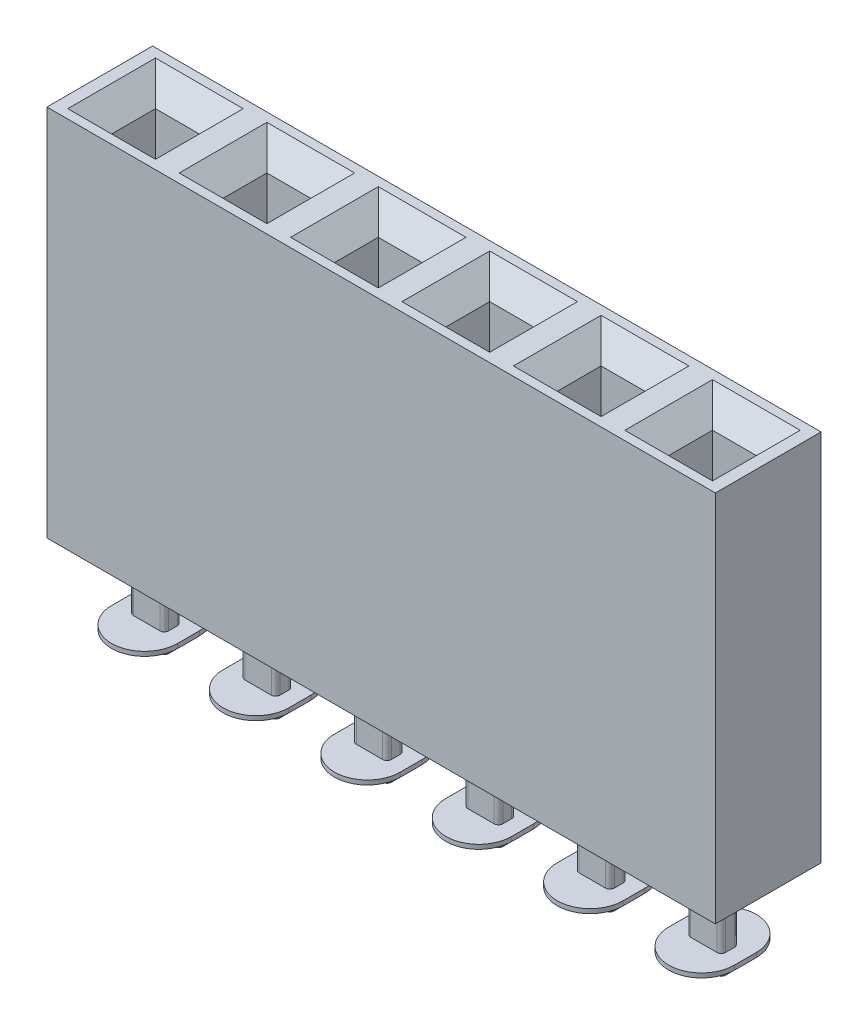
SolidWorks part; units mm, degrees
material "PA Type 6"
ref_plane "Front Plane" through (0, 0, 0) normal (0, 0, 1) x (1, 0, 0)
ref_plane "Top Plane" through (0, 0, 0) normal (0, 1, 0) x (1, 0, 0)
ref_plane "Right Plane" through (0, 0, 0) normal (1, 0, 0) x (0, 0, -1)
ref_plane "Plane1" through (0, -1.65, 0) normal (0, 1, 0) x (1, 0, 0)
sketch "Sketch2" plane through (0, 0, 0) normal (0, 1, 0) x (1, 0, 0)
  line L0 (0, -55) -> (0, 55) construction
  line L1 (-1.27, 1.205) -> (13.97, 1.205)
  line L2 (-1.27, 1.205) -> (-1.27, -1.205)
  line L3 (-1.27, -1.205) -> (13.97, -1.205)
  line L4 (13.97, 1.205) -> (13.97, -1.205)
  line L5 (-55, 0) -> (55, 0) construction
  dimension "D1" = 15.24
  dimension "D2" = 1.27
  dimension "D3" = 2.41
  dimension "D4" = 1.205
extrude "Boss-Extrude1" add sketch "Sketch2" along normal blind 8.51
sketch "Sketch5" plane through (0, 8.51, 0) normal (0, 1, 0) x (1, 0, 0)
  line L0 (-55, 0) -> (55, 0) construction
  line L1 (0.5, 0.5) -> (-0.5, 0.5)
  line L2 (0.5, 0.5) -> (0.5, -0.5)
  line L3 (0.5, -0.5) -> (-0.5, -0.5)
  line L4 (-0.5, 0.5) -> (-0.5, -0.5)
  line L5 (0, -55) -> (0, 55) construction
  dimension "D1" = 0.5
  dimension "D2" = 1
  dimension "D3" = 0.5
extrude "Cut-Extrude1" cut sketch "Sketch5" against normal blind 5
chamfer "Chamfer1" distance 0.5 angle 45 4 edges at (-0.5, 8.51, 0) (0, 8.51, 0.5) (0.5, 8.51, 0) (0, 8.51, -0.5)
pattern_linear "LPattern3" count 6 spacing 2.54 along (1, 0, 0) of "Chamfer1", "Cut-Extrude1"
sketch "Sketch8" plane through (0, 0, 0) normal (0, 1, 0) x (1, 0, 0)
  line L0 (0, -1.3255) -> (0, 1.3255) construction
  line L1 (-0.3, -0.2) -> (0.3, -0.2)
  line L2 (-0.4, -0.1) -> (-0.4, 0.1)
  line L3 (-0.3, 0.2) -> (0.3, 0.2)
  line L4 (0.4, -0.1) -> (0.4, 0.1)
  line L5 (-4.6805, 0) -> (4.6805, 0) construction
  arc A0 (-0.3, -0.2) -> (-0.4, -0.1) centre (-0.3, -0.1) cw
  arc A1 (0.3, -0.2) -> (0.4, -0.1) centre (0.3, -0.1) ccw
  arc A2 (0.3, 0.2) -> (0.4, 0.1) centre (0.3, 0.1) cw
  arc A3 (-0.4, 0.1) -> (-0.3, 0.2) centre (-0.3, 0.1) cw
  point P10 (-0.4, -0.2)
  point P13 (0.4, -0.2)
  point P16 (0.4, 0.2)
  dimension "D5" = 0.1
  dimension "D1" = 0.4
  dimension "D2" = 0.8
  dimension "D3" = 0.4
  dimension "D4" = 0.2
extrude "Boss-Extrude2" add sketch "Sketch8" against normal blind 2 separate body
sketch "Sketch10" plane through (0, -1.65, 0) normal (0, 1, 0) x (1, 0, 0)
  line L0 (0, -0.25) -> (0, 0.25) construction
  line L1 (0, -1.3255) -> (0, 1.3255) construction
  line L2 (-0.75, -0.25) -> (-0.75, 0.25)
  line L3 (0.75, -0.25) -> (0.75, 0.25)
  line L4 (-5.7805, 0) -> (5.7805, 0) construction
  arc A0 (-0.75, -0.25) -> (0.75, -0.25) centre (0, -0.25) ccw
  arc A1 (0.75, 0.25) -> (-0.75, 0.25) centre (0, 0.25) ccw
  point P5 (0, 0)
  dimension "D1" = 1.5
  dimension "D2" = 0.5
extrude "Boss-Extrude3" add sketch "Sketch10" along normal blind 0.1
fillet "Fillet2" radius 0.4 6 edges at (-0.3707, -1.65, -0.1707) (-0.3707, -1.65, 0.1707) (0, -1.65, 0.2) (0.3707, -1.65, 0.1707) (0.3707, -1.65, -0.1707) (0, -1.65, -0.2)
ref_axis "Axis1" through (0, -2.5255, 0) along (0, 1, 0)
pattern_linear "Répétition linéaire1" count 6 spacing 2.54 along (1, 0, 0) of bodies 105
equation "\"D1@Sketch2\"=2.54 *6"
